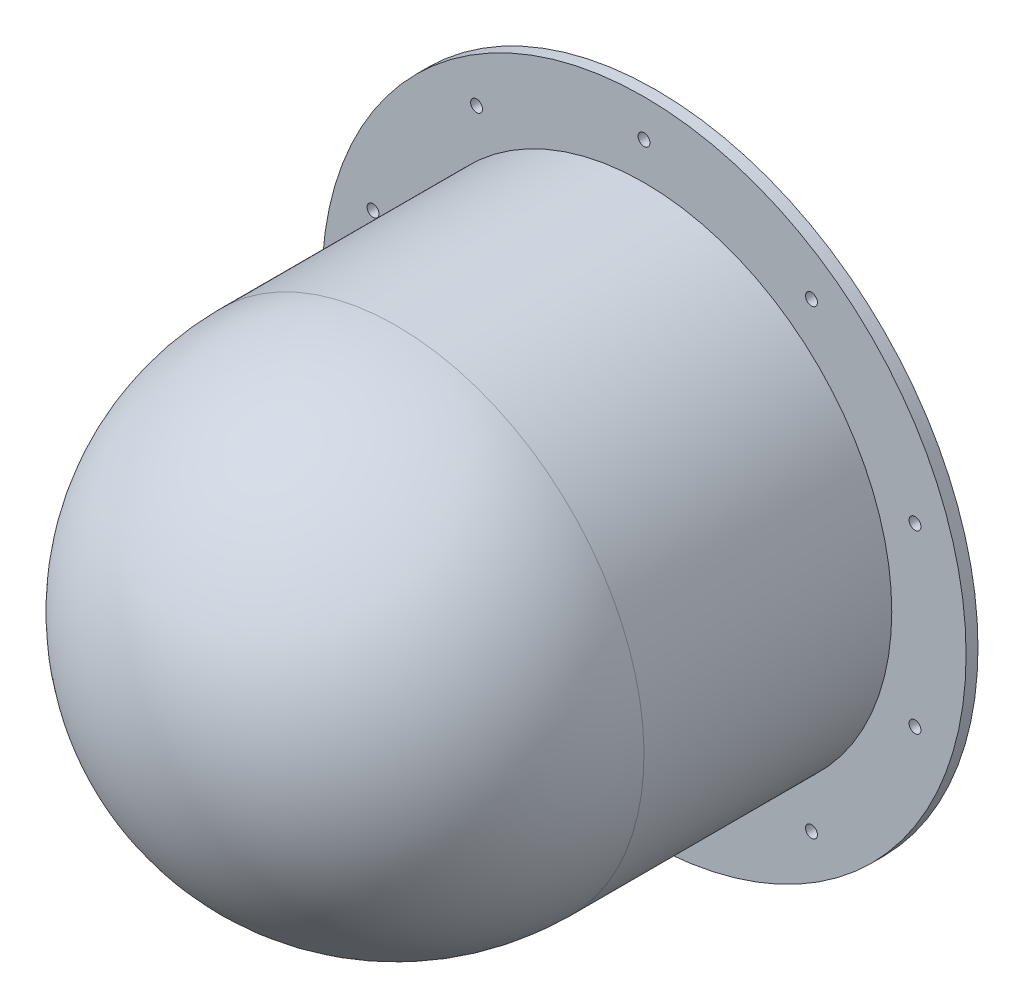
SolidWorks part; units mm, degrees
ref_plane "Front Plane" through (0, 0, 0) normal (0, 0, 1) x (1, 0, 0)
ref_plane "Top Plane" through (0, 0, 0) normal (0, 1, 0) x (1, 0, 0)
ref_plane "Right Plane" through (0, 0, 0) normal (1, 0, 0) x (0, 0, -1)
sketch "Sketch1" plane through (0, 0, 0) normal (0, 0, 1) x (1, 0, 0)
  circle A0 centre (0, 0) radius 325
  circle A1 centre (0, 0) radius 250 construction
  circle A2 centre (0, 0) radius 287.5 construction
  circle A3 centre (0, 287.5) radius 6
  circle A4 centre (168.9883, 232.5924) radius 6
  circle A5 centre (273.4287, 88.8424) radius 6
  circle A6 centre (273.4287, -88.8424) radius 6
  circle A7 centre (168.9883, -232.5924) radius 6
  circle A8 centre (0, -287.5) radius 6
  circle A9 centre (-168.9883, -232.5924) radius 6
  circle A10 centre (-273.4287, -88.8424) radius 6
  circle A11 centre (-273.4287, 88.8424) radius 6
  circle A12 centre (-168.9883, 232.5924) radius 6
  circle A13 centre (0, 0) radius 244
  point P28 (0, 0)
  dimension "D1" = 650
  dimension "D2" = 500
  dimension "D3" = 575
  dimension "D4" = 12
  dimension "D5" = 6
extrude "Boss-Extrude1" add sketch "Sketch1" along normal blind 12
sketch "Sketch3" plane through (0, 0, 12) normal (0, 0, 1) x (1, 0, 0)
  circle A0 centre (0, 0) radius 244
  circle A1 centre (0, 0) radius 244 construction
  circle A2 centre (0, 0) radius 250
  dimension "D1" = 6
extrude "Boss-Extrude2" [suppressed] add sketch "Sketch3" along normal blind 200 from surface
sketch "Sketch2" [suppressed] plane through (0, 0, 200) normal (0, 0, 1) x (1, 0, 0)
  line L0 (0, 300) -> (0, 294)
  line L1 (0, -294) -> (0, -300)
  arc A0 (0, 300) -> (0, -300) centre (0, 0) ccw
  circle A1 centre (0, 0) radius 300 construction
  arc A2 (0, 294) -> (0, -294) centre (0, 0) ccw
  circle A3 centre (0, 0) radius 294 construction
revolve "Revolve1" [suppressed] add sketch "Sketch2" angle 180 about L0 reverse direction yes
sketch "Sketch4" plane through (0, 0, 0) normal (1, 0, 0) x (0, 0, -1)
  line L0 (-12, 250) -> (-12, -250) construction
  line L1 (-12, 325) -> (-12, -325) construction
  line L2 (-12, 244) -> (-12, -244) construction
  line L3 (-12, 250) -> (-262, 250)
  line L4 (-12, 0) -> (-512, 0) construction
  line L5 (-12, 244) -> (-262, 244)
  line L6 (-512, 0) -> (-506, 0)
  line L7 (-12, 250) -> (-12, 244)
  arc A0 (-262, 250) -> (-512, 0) centre (-262, 0) ccw
  arc A1 (-262, 244) -> (-506, 0) centre (-262, 0) ccw
  point P6 (-12, 0)
  dimension "D3" = 250
  dimension "D1" = 500
  dimension "D2" = 6
  dimension "D4" = 6
  dimension "D5" = 500
revolve "Revolve2" add sketch "Sketch4" angle 360 about L4
equation "\"mbtOD\" = 500"
equation "\"mbtT\" = 6"
equation "\"mbtL\" = 3000"
equation "\"mbtFlangeOD\" = 650"
equation "\"mbtFlangeT\" = 12"
equation "\"mbtFlangeHoleDia\" = 12"
equation "\"D1@Sketch1\"=\"mbtFlangeOD\""
equation "\"D2@Sketch1\"=\"mbtOD\""
equation "\"D3@Sketch1\"=(\"mbtFlangeOD\"+\"mbtOD\")/2"
equation "\"D4@Sketch1\"=\"mbtFlangeHoleDia\""
equation "\"D1@Boss-Extrude1\"=\"mbtFlangeT\""
equation "\"D5@Sketch1\"=\"mbtT\""
equation "\"D1@Sketch3\"=\"mbtT\""
equation "\"mbtFlangeBoltCircleDia\" = 650"
equation "\"mbtOringSize\" = 10 "
equation "\"mbtOringDia\" = 620"
equation "\"mbtWidth\" = 2250"
equation "\"skiWidth\" = 1250"
equation "\"D1@Sketch4\"=\"mbtOD\""
equation "\"D2@Sketch4\"=\"mbtT\""
equation "\"D3@Sketch4\"=\"mbtOD\"/2"
equation "\"D4@Sketch4\"=\"mbtT\""
equation "\"mbtCapL\" = 500"
equation "\"D5@Sketch4\"=\"mbtCapL\""
